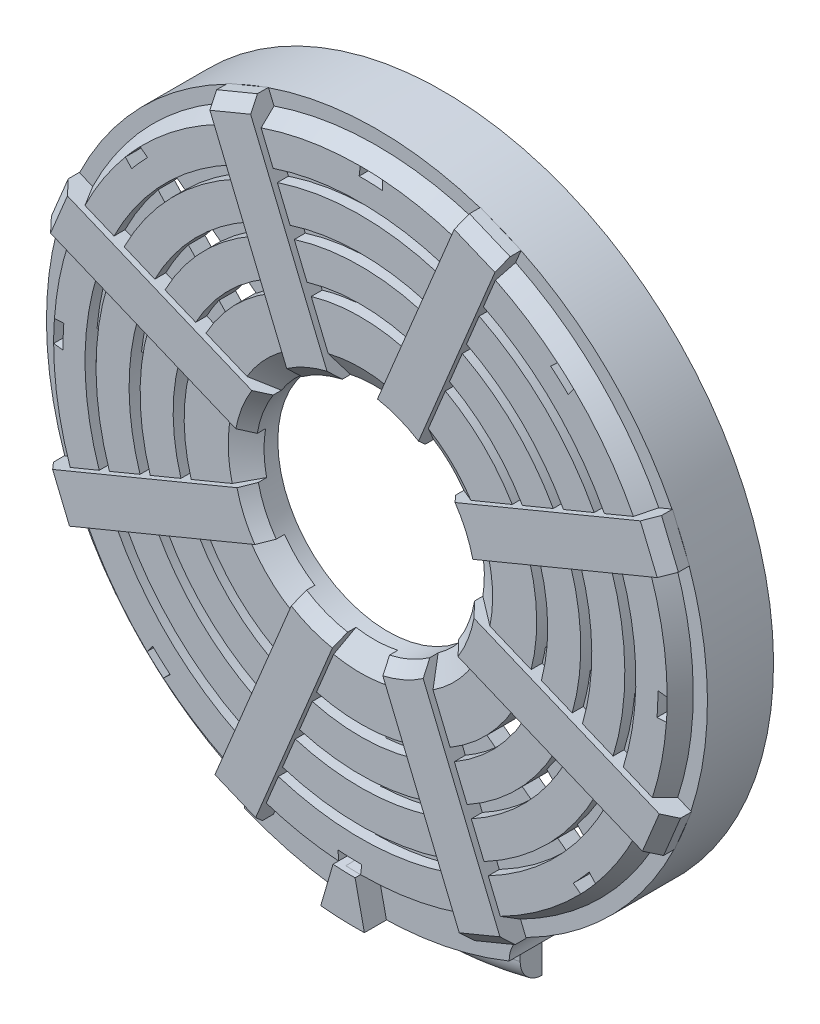
SolidWorks part; units mm, degrees
material "AISI 304"
ref_plane "Front Plane" through (0, 0, 0) normal (0, 0, 1) x (1, 0, 0)
ref_plane "Top Plane" through (0, 0, 0) normal (0, 1, 0) x (1, 0, 0)
ref_plane "Right Plane" through (0, 0, 0) normal (1, 0, 0) x (0, 0, -1)
sketch "草图2" plane through (0, 0, 20) normal (0, 0, 1) x (1, 0, 0)
  line L2 (12, -35.4955) -> (12, -29.3939)
  line L3 (-12, -29.3939) -> (-12, -35.4955)
  circle A1 centre (0, 0) radius 26.9356
  arc A2 (13.6364, -26.7217) -> (-13.6364, -26.7217) centre (0, 0) ccw
  arc A5 (13.6364, -26.7217) -> (12, -29.3939) centre (15, -29.3939) ccw
  arc A6 (-12, -35.4955) -> (12, -35.4955) centre (0, 0) ccw
  arc A7 (-12, -29.3939) -> (-13.6364, -26.7217) centre (-15, -29.3939) ccw
extrude "凸台-拉伸1" add sketch "草图2" along normal blind 2
sketch "草图3" plane through (0, 0, 22) normal (0, 0, 1) x (1, 0, 0)
  line L0 (-9, -36.3721) -> (-9, -28.6182)
  line L1 (0, -37.469) -> (0, -24.2396) construction
  line L2 (9, -36.3721) -> (9, -28.6182)
  line L3 (12, -35.4955) -> (12, -29.3939) construction
  line L4 (-12, -29.3939) -> (-12, -35.4955) construction
  line L5 (12, -35.4955) -> (12, -29.3939)
  line L6 (-12, -29.3939) -> (-12, -35.4955)
  arc A0 (-12, -35.4955) -> (12, -35.4955) centre (0, 0) ccw construction
  circle A1 centre (0, 0) radius 30 construction
  arc A2 (-13.6364, -26.7217) -> (-9, -28.6182) centre (0, 0) ccw
  arc A4 (13.6364, -26.7217) -> (12, -29.3939) centre (15, -29.3939) ccw construction
  arc A5 (-12, -29.3939) -> (-13.6364, -26.7217) centre (-15, -29.3939) ccw construction
  arc A6 (13.6364, -26.7217) -> (12, -29.3939) centre (15, -29.3939) ccw
  arc A7 (-12, -35.4955) -> (-9, -36.3721) centre (0, 0) ccw
  arc A8 (-12, -29.3939) -> (-13.6364, -26.7217) centre (-15, -29.3939) ccw
  arc A9 (9, -28.6182) -> (13.6364, -26.7217) centre (0, 0) ccw
  arc A10 (9, -36.3721) -> (12, -35.4955) centre (0, 0) ccw
  dimension "D1" = 9
extrude "切除-拉伸3" cut sketch "草图3" against normal blind 2
sketch "草图4" plane through (0, 0, 22) normal (0, 0, 1) x (1, 0, 0)
  line L0 (9, -28.6182) -> (9, -36.3721) construction
  line L1 (-9, -36.3721) -> (-9, -28.6182) construction
  line L6 (9, -35) -> (9, -36.3721)
  line L7 (-9, -36.3721) -> (-9, -35)
  arc A0 (-9, -36.3721) -> (9, -36.3721) centre (0, 0) ccw construction
  arc A1 (-9, -36.3721) -> (9, -36.3721) centre (0, 0) ccw
  arc A5 (-9, -35) -> (9, -35) centre (0, 0) ccw
extrude "切除-拉伸4" cut sketch "草图4" against normal blind 2
fillet "圆角2" radius 2 1 edges at (0, -36.1386, 22)
sketch "草图7" plane through (0, 0, 22) normal (0, 0, 1) x (1, 0, 0)
  line L2 (-9, -28.6182) -> (-9, -32.9309)
  line L3 (9, -32.9309) -> (9, -28.6182)
  line L4 (-9, -30.4467) -> (-9, -32.9309)
  line L5 (9, -32.9309) -> (9, -30.4467)
  arc A0 (-12, -29.3939) -> (-13.6364, -26.7217) centre (-15, -29.3939) ccw construction
  arc A2 (-9, -32.9309) -> (9, -32.9309) centre (0, 0) ccw
  arc A3 (9, -28.6182) -> (-9, -28.6182) centre (0, 0) ccw
  arc A4 (-9, -32.9309) -> (9, -32.9309) centre (0, 0) ccw
  arc A5 (9, -28.6182) -> (13.6364, -26.7217) centre (0, 0) ccw
  arc A6 (13.6364, -26.7217) -> (12, -29.3939) centre (15, -29.3939) ccw construction
  arc A7 (13.6364, -26.7217) -> (12, -29.3939) centre (15, -29.3939) ccw
  arc A8 (9, -28.6182) -> (-9, -28.6182) centre (0, 0) ccw construction
  arc A9 (9, -28.6182) -> (13.6364, -26.7217) centre (0, 0) ccw
  arc A10 (13.6364, -26.7217) -> (12, -29.3939) centre (15, -29.3939) ccw
  arc A11 (-12, -29.3939) -> (-13.6364, -26.7217) centre (-15, -29.3939) ccw
  arc A12 (-12, -29.3939) -> (12, -29.3939) centre (0, 0) ccw
  arc A13 (-13.6364, -26.7217) -> (13.6364, -26.7217) centre (0, 0) ccw
  arc A14 (-13.6364, -26.7217) -> (-9, -28.6182) centre (0, 0) ccw
  arc A15 (-13.6364, -26.7217) -> (-9, -28.6182) centre (0, 0) ccw
  line M7 (-9, -28.6182) -> (-9, -32.9309)
  line M9 (9, -32.9309) -> (9, -28.6182)
  arc M10 (9, -28.6182) -> (-9, -28.6182) centre (0, 0) ccw
  dimension "D1" = 0
extrude "凸台-拉伸2" add sketch "草图7" against normal blind 2 contours A11 A12 M7 M10 | A13 A12 M7 M9 | A12 A7 M9 M10 region at (0, -30.4259, 22) region at (-10.6878, -28.8911, 22) region at (10.6878, -28.8911, 22)
sketch "草图8" plane through (0, 0, 22) normal (0, 0, 1) x (1, 0, 0)
  arc A0 (-12, -29.3939) -> (12, -29.3939) centre (0, 0) ccw
  arc A1 (13.6364, -26.7217) -> (12, -29.3939) centre (15, -29.3939) ccw construction
  circle A2 centre (0, 0) radius 30 construction
  arc A3 (-12, -29.3939) -> (-13.6364, -26.7217) centre (-15, -29.3939) ccw construction
  arc A4 (13.6364, -26.7217) -> (12, -29.3939) centre (15, -29.3939) ccw
  arc A5 (-13.6364, -26.7217) -> (13.6364, -26.7217) centre (0, 0) ccw
  arc A6 (-12, -29.3939) -> (-13.6364, -26.7217) centre (-15, -29.3939) ccw
extrude "凸台-拉伸3" add sketch "草图8" along normal blind 4
sketch "草图9" plane through (0, 0, 22) normal (0, 0, 1) x (1, 0, 0)
  circle A3 centre (0, 0) radius 27
  circle A4 centre (0, 0) radius 30
extrude "凸台-拉伸5" add sketch "草图9" along normal blind 4
sketch "草图10" plane through (0, 0, 26) normal (0, 0, 1) x (1, 0, 0)
  circle A0 centre (0, 0) radius 29
extrude "凸台-拉伸6" add sketch "草图10" along normal up to surface (1.5 mm away)
chamfer "倒角1" distance 2 angle 30 1 edges at (29, 0, 27.5) first distance on face at (29, 0, 26)
sketch "草图12" plane through (0, 0, 27.5) normal (0, 0, 1) x (1, 0, 0)
  circle A0 centre (0, 0) radius 10
extrude "切除-拉伸5" cut sketch "草图12" against normal blind 18
sketch "草图13" plane through (0, 0, 20) normal (0, 0, -1) x (-1, 0, 0)
  circle A0 centre (0, 0) radius 27
extrude "凸台-拉伸7" add sketch "草图13" against normal up to surface (6 mm away) up to face at (10, 0, 26)
sketch "草图14" plane through (0, 0, 27.5) normal (0, 0, 1) x (1, 0, 0)
  circle A0 centre (0, 0) radius 10
extrude "切除-拉伸6" cut sketch "草图14" against normal blind 8
sketch "草图16" plane through (0, 0, 20) normal (0, 0, -1) x (-1, 0, 0)
  circle A0 centre (0, 0) radius 27
extrude "切除-拉伸7" cut sketch "草图16" against normal blind 5
chamfer "倒角2" distance 2 angle 32 1 edges at (10, 0, 27.5) first distance on face at (10, 0, 27.5)
sketch "草图17" plane through (0, 0, 27.5) normal (0, 0, 1) x (1, 0, 0)
  circle A0 centre (0, 0) radius 25
  circle A1 centre (0, 0) radius 24
  circle A2 centre (0, 0) radius 21
  circle A3 centre (0, 0) radius 20
  circle A4 centre (0, 0) radius 17
  circle A5 centre (0, 0) radius 16
  dimension "D1" = 50
  dimension "D2" = 48
  dimension "D3" = 42
  dimension "D4" = 40
  dimension "D5" = 34
  dimension "D6" = 32
extrude "切除-拉伸10" cut sketch "草图17" against normal blind 1 contours A0 A1 | A2 A3 | A4 A5 region at (-24.2929, 0, 27.5) region at (-20.406, 0, 27.5) region at (-16.5192, 0, 27.5)
sketch "草图18" plane through (0, 0, 0) normal (0, 1, 0) x (1, 0, 0)
  line L0 (0, -20) -> (0, -40.9012) construction
  line L1 (-10.5, -23.7655) -> (-7.5, -23.7655)
  line L2 (-10.5, -23.7655) -> (-10.5, -22.7655)
  line L3 (-4.5, -23.7655) -> (-1.5, -23.7655)
  line L4 (-4.5, -23.7655) -> (-4.5, -22.7655)
  line L5 (-4.5, -22.7655) -> (-1.5, -22.7655)
  line L6 (-1.5, -23.7655) -> (-1.5, -22.7655)
  line L7 (-10.5, -22.7655) -> (-7.5, -22.7655)
  line L8 (-7.5, -23.7655) -> (-7.5, -22.7655)
  line L9 (7.5, -23.7655) -> (7.5, -22.7655)
  line L10 (10.5, -22.7655) -> (7.5, -22.7655)
  line L11 (1.5, -23.7655) -> (1.5, -22.7655)
  line L12 (4.5, -22.7655) -> (1.5, -22.7655)
  line L13 (4.5, -23.7655) -> (4.5, -22.7655)
  line L14 (4.5, -23.7655) -> (1.5, -23.7655)
  line L15 (10.5, -23.7655) -> (10.5, -22.7655)
  line L16 (10.5, -23.7655) -> (7.5, -23.7655)
  dimension "D1" = 1.5
  dimension "D2" = 2
extrude "切除-拉伸11" cut sketch "草图18" against normal blind 71
sketch "草图25" plane through (0, 0, 25) normal (0, 0, -1) x (-1, 0, 0)
  circle A0 centre (0, 0) radius 10.0206
  circle A1 centre (0, 0) radius 10.8
extrude "凸台-拉伸18" add sketch "草图25" against normal blind 1
sketch "草图26" plane through (0, 0, 27.5) normal (0, 0, 1) x (1, 0, 0)
  line L0 (0, 0.2463) -> (48.6925, 0.2463) construction
  line L1 (0, 0) -> (0, 32.9764) construction
  line L3 (8.1431, 5.8044) -> (26.8317, 13.5455)
  line L5 (9.7667, 2.1473) -> (28.3624, 9.8499)
  line L6 (26.8317, 13.5455) -> (28.3624, 9.8499)
  line L7 (9.8623, -1.6537) -> (28.551, -9.3948)
  line L8 (28.551, -9.3948) -> (27.0202, -13.0903)
  line L9 (8.4245, -5.3877) -> (27.0202, -13.0903)
  line L11 (5.8044, -8.1431) -> (13.5455, -26.8317)
  line L12 (13.5455, -26.8317) -> (9.8499, -28.3624)
  line L13 (2.1473, -9.7667) -> (9.8499, -28.3624)
  line L15 (-1.6537, -9.8623) -> (-9.3948, -28.551)
  line L16 (-9.3948, -28.551) -> (-13.0903, -27.0202)
  line L17 (-5.3877, -8.4245) -> (-13.0903, -27.0202)
  line L19 (-8.1431, -5.8044) -> (-26.8317, -13.5455)
  line L20 (-26.8317, -13.5455) -> (-28.3624, -9.8499)
  line L21 (-9.7667, -2.1473) -> (-28.3624, -9.8499)
  line L23 (-9.8623, 1.6537) -> (-28.551, 9.3948)
  line L24 (-28.551, 9.3948) -> (-27.0202, 13.0903)
  line L25 (-8.4245, 5.3877) -> (-27.0202, 13.0903)
  line L27 (-5.8044, 8.1431) -> (-13.5455, 26.8317)
  line L28 (-13.5455, 26.8317) -> (-9.8499, 28.3624)
  line L29 (-2.1473, 9.7667) -> (-9.8499, 28.3624)
  line L31 (1.6537, 9.8623) -> (9.3948, 28.551)
  line L32 (9.3948, 28.551) -> (13.0903, 27.0202)
  line L33 (5.3877, 8.4245) -> (13.0903, 27.0202)
  circle A0 centre (0, 0) radius 10
  point P43 (0, 0)
  circle M36 centre (0, 0) radius 25
  circle M37 centre (0, 0) radius 27.8453
  dimension "D1" = 8
extrude "凸台-拉伸19" add sketch "草图26" along normal mid plane 3 contours L29 L28 L27 M37 | A0 L29 L27 M36 | L29 L27 M36 M37 | L33 L32 L31 M37 | L33 L31 M36 M37 | A0 L33 L31 M36 | A0 L5 L3 M36 | L5 L3 M36 M37 | L6 L3 L5 M37 | L9 L7 M36 M37 | L9 L8 L7 M37 | A0 L9 L7 M36 | A0 L13 L11 M36 | L13 L11 M36 M37 | L13 L12 L11 M37 | L17 L16 L15 M37 | A0 L17 L15 M36 | L17 L15 M36 M37 | A0 L21 L19 M36 | L21 L19 M36 M37 | L21 L20 L19 M37 | A0 L25 L23 M36 | L25 L23 M36 M37 | L25 L24 L23 M37 region at (16.0277, 6.907, 27.5) region at (24.2924, 10.3294, 27.5) region at (6.4493, 16.2172, 27.5) region at (26.6005, 11.2908, 27.5) region at (9.8734, 24.4813, 27.5) region at (10.8255, 26.7932, 27.5) region at (16.2172, -6.4493, 27.5) region at (-6.907, 16.0277, 27.5) region at (24.4813, -9.8734, 27.5) region at (-10.3294, 24.2924, 27.5) region at (26.7932, -10.8255, 27.5) region at (-11.2908, 26.6005, 27.5) region at (6.907, -16.0277, 27.5) region at (-16.2172, 6.4493, 27.5) region at (10.3294, -24.2924, 27.5) region at (-24.4813, 9.8734, 27.5) region at (11.2908, -26.6005, 27.5) region at (-26.7932, 10.8255, 27.5) region at (-6.4493, -16.2172, 27.5) region at (-16.0277, -6.907, 27.5) region at (-9.8734, -24.4813, 27.5) region at (-24.2924, -10.3294, 27.5) region at (-10.8255, -26.7932, 27.5) region at (-26.6005, -11.2908, 27.5)
chamfer "倒角3" distance 2 angle 45 8 edges at (4.0579, -9.1397, 29) (-3.5934, -9.3321, 29) (-9.1397, -4.0579, 29) (-9.3321, 3.5934, 29) (-4.0579, 9.1397, 29) (3.5934, 9.3321, 29) (9.1397, 4.0579, 29) (9.3321, -3.5934, 29)
chamfer "倒角4" distance 2 angle 45 8 edges at (11.2426, 27.7856, 29) (27.5971, 11.6977, 29) (27.7856, -11.2426, 29) (11.6977, -27.5971, 29) (-11.2426, -27.7856, 29) (-11.6977, 27.5971, 29) (-27.5971, -11.6977, 29) (-27.7856, 11.2426, 29)
sketch "草图30" plane through (0, 0, 27.5) normal (0, 0, 1) x (1, 0, 0)
  line L0 (-11.2426, -27.7856) -> (11.2426, 27.7856) construction
  line L1 (-2.1261, -24.9094) -> (-2.1754, -23.9012)
  line L2 (-12.8439, -16.6143) -> (-12.1044, -15.9212)
  line L3 (-27.7856, 11.2426) -> (27.7856, -11.2426) construction
  line L4 (0.3579, -24.9974) -> (0.4784, -23.9952)
  line L5 (-15.1955, -14.4947) -> (-14.5827, -13.6874)
  line L6 (2.1261, 24.9094) -> (2.1754, 23.9012)
  line L7 (-2.5653, -15.9192) -> (-2.5715, -15.792)
  line L8 (-1.9862, -27.7744) -> (-2.0277, -26.9237)
  line L9 (0.0156, -27.8453) -> (0.1172, -26.9997)
  line L10 (1.4322, -16.0608) -> (1.4474, -15.9344)
  line L11 (-2.5217, -16.8119) -> (-2.5653, -15.9192)
  line L12 (-12.7382, -11.2578) -> (-12.1977, -10.5459)
  line L13 (1.3255, -16.9482) -> (1.4322, -16.0608)
  line L14 (0.8405, -20.9832) -> (0.9615, -19.9769)
  line L15 (-9.8787, -13.8351) -> (-9.2265, -13.2239)
  line L16 (-2.3234, -20.8711) -> (-2.3728, -19.8587)
  line L17 (-12.1977, -10.5459) -> (-12.1208, -10.4445)
  line L18 (-19.3745, -19.9997) -> (-18.8596, -19.3214)
  line L19 (-17.8867, -21.3408) -> (-17.2653, -20.7584)
  line L20 (-9.2265, -13.2239) -> (-9.1336, -13.1368)
  line L21 (-0.3579, 24.9974) -> (-0.4784, 23.9952)
  line L22 (-17.6402, -17.7151) -> (-17.0298, -16.9111)
  line L23 (-15.7938, -19.3792) -> (-15.0574, -18.6889)
  line L24 (2.5653, 15.9192) -> (2.5715, 15.792)
  line L25 (1.9862, 27.7744) -> (2.0277, 26.9237)
  line L26 (-0.0156, 27.8453) -> (-0.1172, 26.9997)
  line L27 (-1.4322, 16.0608) -> (-1.4474, 15.9344)
  line L28 (12.8439, 16.6143) -> (12.1044, 15.9212)
  line L29 (2.5217, 16.8119) -> (2.5653, 15.9192)
  line L30 (15.1955, 14.4947) -> (14.5827, 13.6874)
  line L31 (12.7382, 11.2578) -> (12.1977, 10.5459)
  line L32 (-1.3255, 16.9482) -> (-1.4322, 16.0608)
  line L33 (9.8787, 13.8351) -> (9.2265, 13.2239)
  line L34 (12.1977, 10.5459) -> (12.1208, 10.4445)
  line L35 (19.3745, 19.9997) -> (18.8596, 19.3214)
  line L36 (17.8867, 21.3408) -> (17.2653, 20.7584)
  line L37 (9.2265, 13.2239) -> (9.1336, 13.1368)
  line L38 (-0.8405, 20.9832) -> (-0.9615, 19.9769)
  line L39 (17.6402, 17.7151) -> (17.0298, 16.9111)
  line L40 (2.3234, 20.8711) -> (2.3728, 19.8587)
  line L41 (15.7938, 19.3792) -> (15.0574, 18.6889)
  arc A0 (-8.5459, -26.5015) -> (9.0146, -26.3457) centre (0, 0) ccw construction
  arc A1 (-1.9862, -27.7744) -> (0.0156, -27.8453) centre (0, 0) ccw
  arc A2 (-3.987, -15.4953) -> (4.4659, -15.3641) centre (0, 0) ccw construction
  arc A3 (-2.5715, -15.792) -> (1.4474, -15.9344) centre (0, 0) ccw
  arc A4 (-7.4531, -23.8632) -> (7.9233, -23.7112) centre (0, 0) ccw construction
  arc A5 (-4.3732, -16.4279) -> (4.8507, -16.2933) centre (0, 0) ccw construction
  arc A6 (-7.0688, -22.9354) -> (7.5397, -22.7849) centre (0, 0) ccw construction
  arc A7 (-5.9149, -20.1498) -> (6.3881, -20.0048) centre (0, 0) ccw construction
  arc A8 (-5.5299, -19.2203) -> (6.004, -19.0775) centre (0, 0) ccw construction
  arc A9 (-2.1261, -24.9094) -> (0.3579, -24.9974) centre (0, 0) ccw
  arc A10 (-2.5217, -16.8119) -> (1.3255, -16.9482) centre (0, 0) ccw
  arc A11 (-2.1754, -23.9012) -> (0.4784, -23.9952) centre (0, 0) ccw
  arc A12 (-2.3234, -20.8711) -> (0.8405, -20.9832) centre (0, 0) ccw
  arc A13 (-2.3728, -19.8587) -> (0.9615, -19.9769) centre (0, 0) ccw
  arc A14 (-2.0277, -26.9237) -> (0.1172, -26.9997) centre (0, 0) ccw
  arc A15 (-17.2653, -20.7584) -> (-18.8596, -19.3214) centre (0, 0) cw
  arc A16 (-12.1044, -15.9212) -> (-14.5827, -13.6874) centre (0, 0) cw
  arc A17 (-12.8439, -16.6143) -> (-15.1955, -14.4947) centre (0, 0) cw
  arc A18 (-15.0574, -18.6889) -> (-17.0298, -16.9111) centre (0, 0) cw
  arc A19 (-9.8787, -13.8351) -> (-12.7382, -11.2578) centre (0, 0) cw
  arc A20 (-15.7938, -19.3792) -> (-17.6402, -17.7151) centre (0, 0) cw
  arc A21 (-9.1336, -13.1368) -> (-12.1208, -10.4445) centre (0, 0) cw
  arc A22 (-17.8867, -21.3408) -> (-19.3745, -19.9997) centre (0, 0) cw
  arc A23 (1.9862, 27.7744) -> (-0.0156, 27.8453) centre (0, 0) ccw
  arc A24 (2.5715, 15.792) -> (-1.4474, 15.9344) centre (0, 0) ccw
  arc A25 (2.1261, 24.9094) -> (-0.3579, 24.9974) centre (0, 0) ccw
  arc A26 (2.5217, 16.8119) -> (-1.3255, 16.9482) centre (0, 0) ccw
  arc A27 (2.1754, 23.9012) -> (-0.4784, 23.9952) centre (0, 0) ccw
  arc A28 (2.3234, 20.8711) -> (-0.8405, 20.9832) centre (0, 0) ccw
  arc A29 (2.3728, 19.8587) -> (-0.9615, 19.9769) centre (0, 0) ccw
  arc A30 (2.0277, 26.9237) -> (-0.1172, 26.9997) centre (0, 0) ccw
  arc A31 (17.2653, 20.7584) -> (18.8596, 19.3214) centre (0, 0) cw
  arc A32 (12.1044, 15.9212) -> (14.5827, 13.6874) centre (0, 0) cw
  arc A33 (12.8439, 16.6143) -> (15.1955, 14.4947) centre (0, 0) cw
  arc A34 (15.0574, 18.6889) -> (17.0298, 16.9111) centre (0, 0) cw
  arc A35 (9.8787, 13.8351) -> (12.7382, 11.2578) centre (0, 0) cw
  arc A36 (15.7938, 19.3792) -> (17.6402, 17.7151) centre (0, 0) cw
  arc A37 (9.1336, 13.1368) -> (12.1208, 10.4445) centre (0, 0) cw
  arc A38 (17.8867, 21.3408) -> (19.3745, 19.9997) centre (0, 0) cw
  point P13 (-0.9859, -27.8278)
  point P14 (-0.5665, -15.99)
  point P67 (-10.7121, -11.8849)
  point P68 (-18.6427, -20.6836)
  point P104 (0.9859, 27.8278)
  point P105 (0.5665, 15.99)
  point P106 (10.7121, 11.8849)
  point P107 (18.6427, 20.6836)
extrude "切除-拉伸13" cut sketch "草图30" against normal blind 10
sketch "草图31" plane through (0, 0, 27.5) normal (0, 0, 1) x (1, 0, 0)
  line L0 (27.7856, -11.2426) -> (-27.7856, 11.2426) construction
  line L1 (19.3215, -18.8595) -> (19.9997, -19.3745)
  line L2 (15.8985, -2.5645) -> (16.8122, -2.52)
  line L3 (11.2426, 27.7856) -> (-11.2426, -27.7856) construction
  line L4 (15.8985, -2.5645) -> (15.7923, -2.5697)
  line L5 (16.0402, 1.433) -> (16.9484, 1.3239)
  line L6 (16.0402, 1.433) -> (15.9346, 1.4456)
  line L7 (19.8589, -2.3717) -> (20.8712, -2.3224)
  line L8 (20.7583, -17.2654) -> (21.3408, -17.8867)
  line L9 (19.9769, 0.9603) -> (20.9832, 0.8395)
  line L10 (23.9952, 0.4778) -> (24.9974, 0.3575)
  line L11 (18.6886, -15.0578) -> (19.379, -15.7942)
  line L12 (23.9013, -2.1748) -> (24.9095, -2.1257)
  line L13 (26.9238, -2.0276) -> (27.7744, -1.9862)
  line L14 (16.9115, -17.0294) -> (17.7154, -17.6399)
  line L15 (26.9997, 0.1171) -> (27.8453, 0.0156)
  line L16 (13.6883, -14.5819) -> (14.4955, -15.1948)
  line L17 (15.9205, -12.1053) -> (16.6137, -12.8447)
  line L18 (10.5305, -12.1839) -> (10.4458, -12.1196)
  line L19 (10.5305, -12.1839) -> (11.259, -12.7371)
  line L20 (13.2086, -9.2127) -> (13.1358, -9.1351)
  line L21 (13.2086, -9.2127) -> (13.8342, -9.88)
  line L22 (-15.8985, 2.5645) -> (-16.8122, 2.52)
  line L23 (-15.8985, 2.5645) -> (-15.7923, 2.5697)
  line L24 (-16.0402, -1.433) -> (-16.9484, -1.3239)
  line L25 (-16.0402, -1.433) -> (-15.9346, -1.4456)
  line L26 (-19.8589, 2.3717) -> (-20.8712, 2.3224)
  line L27 (-19.9769, -0.9603) -> (-20.9832, -0.8395)
  line L28 (-23.9952, -0.4778) -> (-24.9974, -0.3575)
  line L29 (-23.9013, 2.1748) -> (-24.9095, 2.1257)
  line L30 (-26.9238, 2.0276) -> (-27.7744, 1.9862)
  line L31 (-26.9997, -0.1171) -> (-27.8453, -0.0156)
  line L32 (-19.3215, 18.8595) -> (-19.9997, 19.3745)
  line L33 (-20.7583, 17.2654) -> (-21.3408, 17.8867)
  line L34 (-18.6886, 15.0578) -> (-19.379, 15.7942)
  line L35 (-16.9115, 17.0294) -> (-17.7154, 17.6399)
  line L36 (-13.6883, 14.5819) -> (-14.4955, 15.1948)
  line L37 (-15.9205, 12.1053) -> (-16.6137, 12.8447)
  line L38 (-10.5305, 12.1839) -> (-10.4458, 12.1196)
  line L39 (-10.5305, 12.1839) -> (-11.259, 12.7371)
  line L40 (-13.2086, 9.2127) -> (-13.1358, 9.1351)
  line L41 (-13.2086, 9.2127) -> (-13.8342, 9.88)
  arc A0 (26.9238, -2.0276) -> (26.9997, 0.1171) centre (0, 0) ccw
  arc A1 (26.5015, -8.5459) -> (26.3457, 9.0146) centre (0, 0) ccw construction
  arc A2 (27.7744, -1.9862) -> (27.8453, 0.0156) centre (0, 0) ccw
  arc A3 (15.4953, -3.987) -> (15.3641, 4.4659) centre (0, 0) ccw construction
  arc A4 (15.7923, -2.5697) -> (15.9346, 1.4456) centre (0, 0) ccw
  arc A5 (23.8632, -7.4531) -> (23.7112, 7.9233) centre (0, 0) ccw construction
  arc A6 (22.9354, -7.0688) -> (22.7849, 7.5397) centre (0, 0) ccw construction
  arc A7 (20.1498, -5.9149) -> (20.0048, 6.3881) centre (0, 0) ccw construction
  arc A8 (19.2203, -5.5299) -> (19.0775, 6.004) centre (0, 0) ccw construction
  arc A9 (16.4279, -4.3732) -> (16.2933, 4.8507) centre (0, 0) ccw construction
  arc A10 (24.9095, -2.1257) -> (24.9974, 0.3575) centre (0, 0) ccw
  arc A11 (23.9013, -2.1748) -> (23.9952, 0.4778) centre (0, 0) ccw
  arc A12 (20.8712, -2.3224) -> (20.9832, 0.8395) centre (0, 0) ccw
  arc A13 (19.8589, -2.3717) -> (19.9769, 0.9603) centre (0, 0) ccw
  arc A14 (16.8122, -2.52) -> (16.9484, 1.3239) centre (0, 0) ccw
  arc A15 (13.8342, -9.88) -> (11.259, -12.7371) centre (0, 0) cw
  arc A16 (15.9205, -12.1053) -> (13.6883, -14.5819) centre (0, 0) cw
  arc A17 (16.6137, -12.8447) -> (14.4955, -15.1948) centre (0, 0) cw
  arc A18 (18.6886, -15.0578) -> (16.9115, -17.0294) centre (0, 0) cw
  arc A19 (19.379, -15.7942) -> (17.7154, -17.6399) centre (0, 0) cw
  arc A20 (13.1358, -9.1351) -> (10.4458, -12.1196) centre (0, 0) cw
  arc A21 (21.3408, -17.8867) -> (19.9997, -19.3745) centre (0, 0) cw
  arc A22 (20.7583, -17.2654) -> (19.3215, -18.8595) centre (0, 0) cw
  arc A23 (-26.9238, 2.0276) -> (-26.9997, -0.1171) centre (0, 0) ccw
  arc A24 (-27.7744, 1.9862) -> (-27.8453, -0.0156) centre (0, 0) ccw
  arc A25 (-15.7923, 2.5697) -> (-15.9346, -1.4456) centre (0, 0) ccw
  arc A26 (-24.9095, 2.1257) -> (-24.9974, -0.3575) centre (0, 0) ccw
  arc A27 (-23.9013, 2.1748) -> (-23.9952, -0.4778) centre (0, 0) ccw
  arc A28 (-20.8712, 2.3224) -> (-20.9832, -0.8395) centre (0, 0) ccw
  arc A29 (-19.8589, 2.3717) -> (-19.9769, -0.9603) centre (0, 0) ccw
  arc A30 (-16.8122, 2.52) -> (-16.9484, -1.3239) centre (0, 0) ccw
  arc A31 (-13.8342, 9.88) -> (-11.259, 12.7371) centre (0, 0) cw
  arc A32 (-15.9205, 12.1053) -> (-13.6883, 14.5819) centre (0, 0) cw
  arc A33 (-16.6137, 12.8447) -> (-14.4955, 15.1948) centre (0, 0) cw
  arc A34 (-18.6886, 15.0578) -> (-16.9115, 17.0294) centre (0, 0) cw
  arc A35 (-19.379, 15.7942) -> (-17.7154, 17.6399) centre (0, 0) cw
  arc A36 (-13.1358, 9.1351) -> (-10.4458, 12.1196) centre (0, 0) cw
  arc A37 (-21.3408, 17.8867) -> (-19.9997, 19.3745) centre (0, 0) cw
  arc A38 (-20.7583, 17.2654) -> (-19.3215, 18.8595) centre (0, 0) cw
  point P11 (27.8278, -0.9859)
  point P15 (15.9694, -0.5658)
  point P65 (11.8696, -10.6983)
  point P66 (20.6836, -18.6427)
  point P85 (-27.8278, 0.9859)
  point P86 (-15.9694, 0.5658)
  point P105 (-11.8696, 10.6983)
  point P106 (-20.6836, 18.6427)
extrude "切除-拉伸14" cut sketch "草图31" against normal blind 10
sketch "草图32" plane through (0, 0, 26) normal (0, 0, 1) x (1, 0, 0)
  line L0 (-0.9859, -27.8278) -> (0, 0) construction
  line L2 (-1.9862, -27.7744) -> (-3.1049, -31.5968)
  line L3 (0.0156, -27.8453) -> (0.861, -31.7373)
  arc A1 (-1.9862, -27.7744) -> (0.0156, -27.8453) centre (0, 0) ccw construction
  arc A2 (-9, -30.4467) -> (9, -30.4467) centre (0, 0) ccw construction
  arc A3 (-1.9862, -27.7744) -> (0.0156, -27.8453) centre (0, 0) ccw
  arc A4 (-3.1049, -31.5968) -> (0.861, -31.7373) centre (0, 0) ccw
  point P9 (-1.1242, -31.7291)
  point P13 (-1.1242, -31.7291)
extrude "凸台-拉伸20" add sketch "草图32" along normal blind 3 separate body
sketch "草图34" plane through (0, 0, 29) normal (0, 0, 1) x (1, 0, 0)
  circle A0 centre (0, 0) radius 44.8882
extrude "切除-拉伸15" cut sketch "草图34" against normal blind 1
ref_plane "基准面1" through (-1.4474, 15.9344, 26.5) normal (0, 0, 1) x (1, 0, 0)
